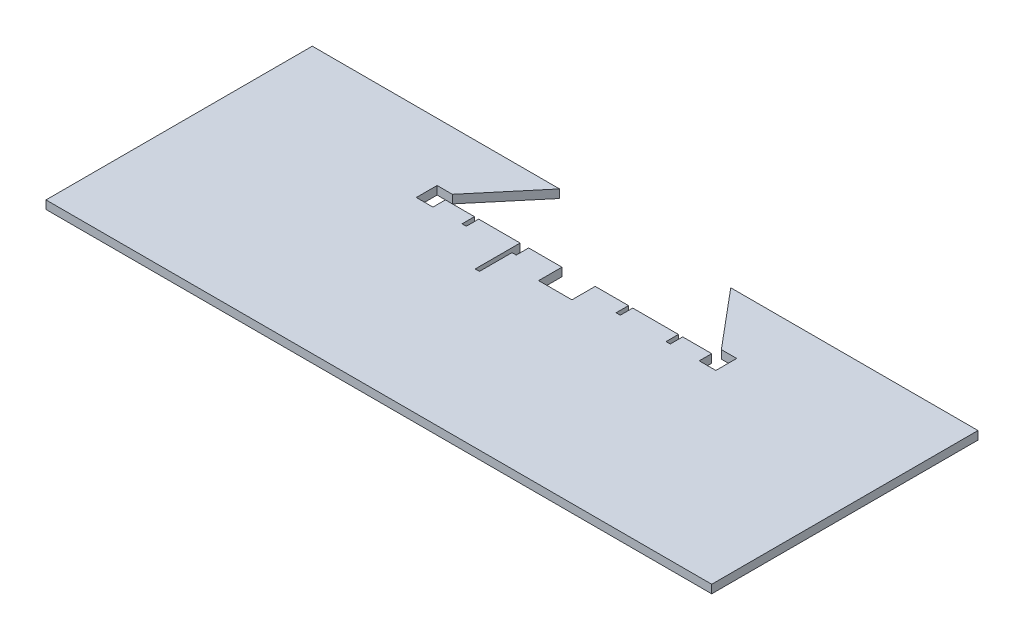
SolidWorks part; units mm, degrees
material "Depron"
ref_plane "Front Plane" through (0, 0, 0) normal (0, 0, 1) x (1, 0, 0)
ref_plane "Top Plane" through (0, 0, 0) normal (0, 1, 0) x (1, 0, 0)
ref_plane "Right Plane" through (0, 0, 0) normal (1, 0, 0) x (0, 0, -1)
sketch "Sketch1" plane through (0, 0, 0) normal (0, 1, 0) x (1, 0, 0)
  line L0 (32.6619, 101.6) -> (127, 101.6)
  line L1 (-127, 0) -> (127, 0)
  line L2 (-127, 0) -> (-127, 101.6)
  line L3 (-127, 101.6) -> (-32.6619, 101.6)
  line L4 (127, 0) -> (127, 101.6)
  line L5 (0, -898.4) -> (0, 49101.6) construction
  line L6 (-53.975, 76.2) -> (-32.6619, 101.6)
  line L7 (-53.975, 76.2) -> (53.975, 76.2)
  line L8 (53.975, 76.2) -> (32.6619, 101.6)
  line L9 (-1003.9539, 76.2) -> (48996.0461, 76.2) construction
  point P11 (0, 76.2)
  dimension "D1" = 101.6
  dimension "D2" = 254
  dimension "D4" = 107.95
  dimension "D6" = 25.4
  dimension "angle1" = 50
extrude "Boss-Extrude1" add sketch "Sketch1" along normal blind 3.175
sketch "Sketch2" plane through (0, 3.175, 0) normal (0, 1, 0) x (-1, 0, 0)
  line L0 (0, 0) -> (0, -134.62) construction
  line L1 (127, 0) -> (-127, 0) construction
  line L2 (-53.975, -76.2) -> (53.975, -76.2) construction
  line L3 (39.7256, -76.2) -> (38.1, -76.2)
  line L4 (39.7256, -76.2) -> (39.7256, -71.4756)
  line L5 (39.7256, -71.4756) -> (38.1, -71.4756)
  line L6 (38.1, -76.2) -> (38.1, -71.4756)
  line L7 (20.6756, -76.2) -> (19.05, -76.2)
  line L8 (-53.975, -76.2) -> (53.975, -76.2) construction
  line L9 (20.6756, -71.4756) -> (19.05, -71.4756)
  line L10 (19.05, -76.2) -> (19.05, -71.4756)
  line L11 (-19.05, -76.2) -> (-19.05, -71.4756)
  line L12 (-20.6756, -71.4756) -> (-19.05, -71.4756)
  line L13 (-20.6756, -76.2) -> (-20.6756, -71.4756)
  line L14 (-20.6756, -76.2) -> (-19.05, -76.2)
  line L15 (-38.1, -76.2) -> (-38.1, -71.4756)
  line L16 (-39.7256, -71.4756) -> (-38.1, -71.4756)
  line L17 (-39.7256, -76.2) -> (-39.7256, -71.4756)
  line L18 (-39.7256, -76.2) -> (-38.1, -76.2)
  line L19 (6.35, -76.2) -> (-6.35, -76.2)
  line L20 (20.6756, -76.2) -> (22.3012, -76.2)
  line L21 (20.6756, -71.4756) -> (20.6756, -59.055)
  line L22 (20.6756, -59.055) -> (22.3012, -59.055)
  line L23 (22.3012, -76.2) -> (22.3012, -59.055)
  line L24 (6.35, -76.2) -> (6.35, -67.31)
  line L25 (6.35, -67.31) -> (-6.35, -67.31)
  line L26 (-6.35, -76.2) -> (-6.35, -67.31)
  line L27 (-53.975, -76.2) -> (-51.3109, -79.375)
  line L28 (50.8, -80.9625) -> (57.15, -80.9625) construction
  line L29 (50.8, -80.9625) -> (50.8, -71.4375) construction
  line L30 (50.8, -71.4375) -> (57.15, -71.4375)
  line L31 (57.15, -80.9625) -> (57.15, -71.4375) construction
  line L32 (50.8, -80.9625) -> (57.15, -71.4375) construction
  line L33 (50.8, -71.4375) -> (57.15, -80.9625) construction
  line L34 (-50.8, -76.2) -> (-53.975, -76.2)
  line L35 (-50.8, -76.2) -> (-50.8, -71.4375)
  line L36 (-50.8, -71.4375) -> (-57.15, -71.4375)
  line L37 (53.975, -76.2) -> (32.6619, -101.6) construction
  line L38 (53.975, -76.2) -> (51.3109, -79.375)
  line L39 (51.3109, -79.375) -> (57.15, -79.375)
  line L40 (57.15, -79.375) -> (57.15, -71.4375)
  line L41 (50.8, -76.2) -> (50.8, -71.4375)
  line L42 (50.8, -76.2) -> (53.975, -76.2)
  line L43 (-57.15, -79.375) -> (-57.15, -71.4375)
  line L44 (-51.3109, -79.375) -> (-57.15, -79.375)
  point P31 (0, -67.31)
  point P32 (53.975, -76.2)
  dimension "D1" = 1.6256
  dimension "D2" = 4.7244
  dimension "D3" = 1.6256
  dimension "D4" = 4.7244
  dimension "D5" = 1.6256
  dimension "D6" = 17.145
  dimension "D7" = 19.05
  dimension "D8" = 38.1
  dimension "D9" = 12.7
  dimension "D10" = 8.89
  dimension "D11" = 6.35
  dimension "D12" = 9.525
  dimension "D13" = 3.175
ref_plane "Center Plane" through (0, 0, 0) normal (1, 0, 0) x (0, 0, -1)
extrude "Cut-Extrude1" cut sketch "Sketch2" against normal up to surface (3.175 mm away) up to face at (0, 0, -69.85)
